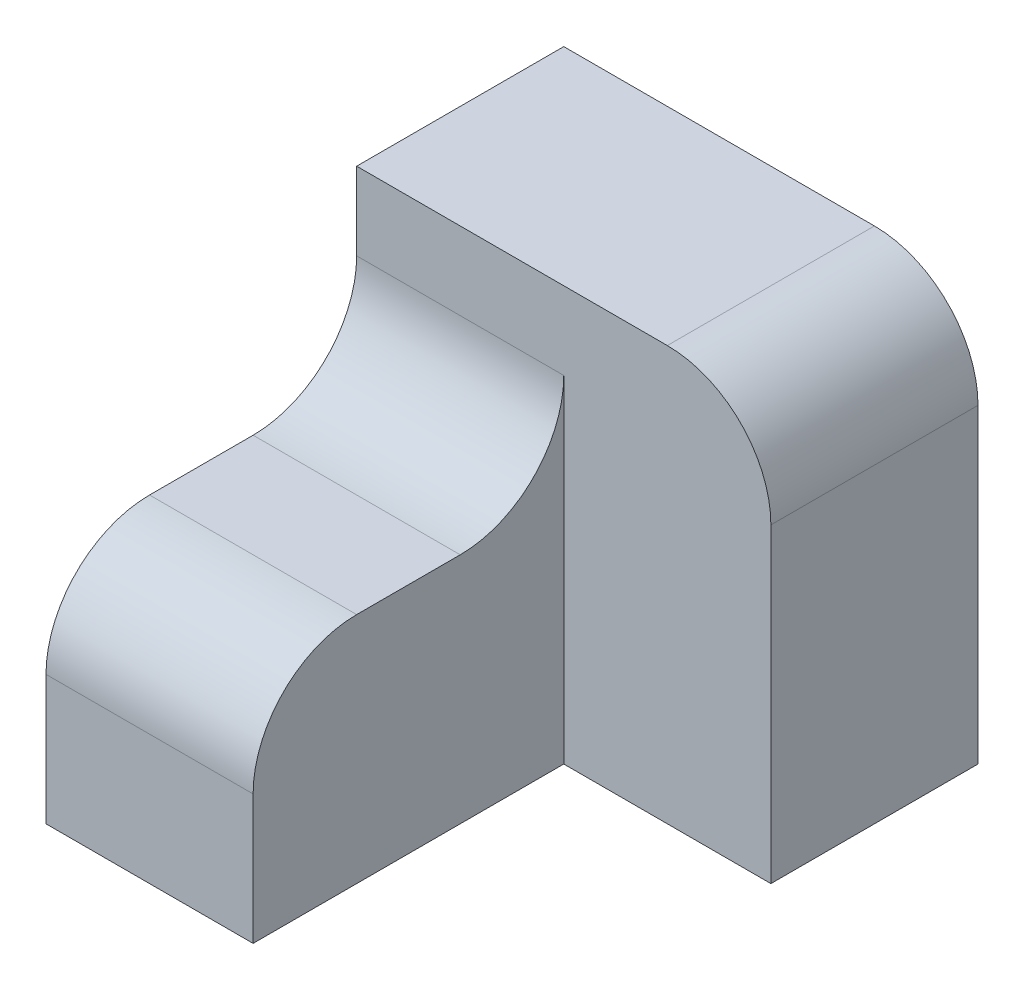
SolidWorks part; units mm, degrees
ref_plane "Front Plane" through (0, 0, 0) normal (0, 0, 1) x (1, 0, 0)
ref_plane "Top Plane" through (0, 0, 0) normal (0, 1, 0) x (1, 0, 0)
ref_plane "Right Plane" through (0, 0, 0) normal (1, 0, 0) x (0, 0, -1)
sketch "Sketch1" plane through (0, 0, 0) normal (0, 0, 1) x (1, 0, 0)
  line L1 (-30, -22.5) -> (-10, -22.5)
  line L2 (-10, -22.5) -> (-10, 0)
  line L3 (-10, 0) -> (-30, 0)
  line L4 (-30, 0) -> (-30, -22.5)
  dimension "D1" = 20
  dimension "Width" = 22.5
extrude "Boss-Extrude1" add sketch "Sketch1" along normal blind 30
sketch "Sketch2" plane through (0, 0, 0) normal (0, 0, 1) x (1, 0, 0)
  line L1 (-30, -22.5) -> (10, -22.5)
  line L2 (10, -22.5) -> (10, 17.5)
  line L3 (10, 17.5) -> (-30, 17.5)
  line L4 (-30, 17.5) -> (-30, -22.5)
  dimension "D1" = 40
  dimension "Width" = 40
extrude "Boss-Extrude2" add sketch "Sketch2" against normal blind 20
fillet "Fillet1" radius 10 3 edges at (-20, 0, 0) (10, 17.5, -10) (-20, 0, 30)
